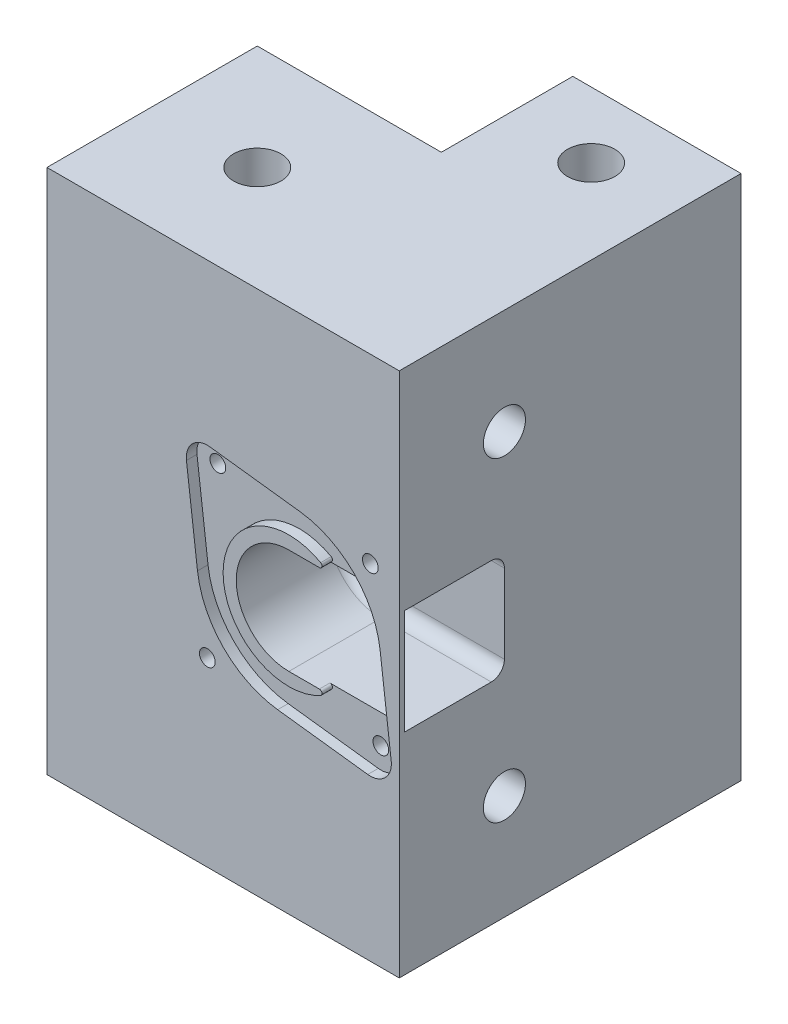
SolidWorks part; units mm, degrees
ref_plane "Front Plane" through (0, 0, 0) normal (0, 0, 1) x (1, 0, 0)
ref_plane "Top Plane" through (0, 0, 0) normal (0, 1, 0) x (1, 0, 0)
ref_plane "Right Plane" through (0, 0, 0) normal (1, 0, 0) x (0, 0, -1)
sketch "Sketch1" plane through (0, 0, 0) normal (0, 1, 0) x (1, 0, 0)
  line L19 (0, -40) -> (0, 0) construction
  line L24 (-25, 0) -> (-5, -40) construction
  line L25 (0, 25) -> (-25, 25) construction
  line L26 (-25, 25) -> (-25, 0) construction
  line L27 (0, 25) -> (32, 0) construction
  line L28 (32, 0) -> (0, 0) construction
  line L29 (-35, 0) -> (0, 0)
  line L30 (-35, -40) -> (-35, 0)
  line L31 (32, -40) -> (-35, -40)
  line L32 (32, 25) -> (32, -40)
  line L33 (0, 25) -> (32, 25)
  line L34 (0, 0) -> (0, 25)
  line L35 (-5, 5) -> (-5, -40) construction
  line L36 (-25, 25) -> (-5, 25) construction
  line L37 (-25, 25) -> (-25, 5) construction
  line L38 (-25, 5) -> (-5, 5) construction
  line L39 (-5, 25) -> (-5, 5) construction
  line L40 (16, 12.5) -> (-5, 22.5) construction
  line L41 (-25, 2.5) -> (-5, 2.5) construction
  line L42 (-25, 2.5) -> (-25, 22.5) construction
  line L43 (-25, 22.5) -> (-5, 22.5) construction
  line L44 (-5, 2.5) -> (-5, 22.5) construction
  line L45 (-25, 2.5) -> (-5, 22.5) construction
  line L46 (-25, 22.5) -> (-5, 2.5) construction
  line L47 (16, 12.5) -> (-5, 2.5) construction
  circle A10 centre (-15, -20) radius 16 construction
  circle A11 centre (-15, -20) radius 6.75 construction
  circle A12 centre (16, 12.5) radius 6 construction
  circle A13 centre (16, 12.5) radius 11 construction
  circle A14 centre (-15, -20) radius 4.5
  circle A15 centre (16, 12.5) radius 4.5
  point P1 (-15, 12.5)
  dimension "D4" = 40
  dimension "D6" = 9
  dimension "D3" = 32
  dimension "D5" = 20
  dimension "D7" = 13.5
  dimension "D8" = 32
  dimension "D9" = 9
  dimension "D10" = 12
  dimension "D11" = 22
  dimension "D1" = 25
  dimension "D2" = 25
  dimension "D12" = 20
extrude "Boss-Extrude1" add sketch "Sketch1" along normal blind 100
sketch "Sketch4" plane through (0, 0, 0) normal (0, -1, 0) x (-1, 0, 0)
  point P0 (15, -20)
hole_wizard "CBORE for M5 Hex Head Bolt2" positions "Sketch4" profile "Sketch5" counterbore size "M5" standard "ANSI Metric"
sketch "Sketch5" plane through (-15, 0, 20) normal (1, 0, 0) x (0, 0, -1)
  line L0 (0, 0) -> (0, 23.85)
  line L1 (0, 23.85) -> (6.75, 23.85)
  line L2 (6.75, 23.85) -> (6.75, 5)
  line L3 (6.75, 5) -> (16, 5)
  line L4 (16, 5) -> (16, 0)
  line L5 (16, 0) -> (0, 0)
  line L10 (0, 23.85) -> (-6.75, 23.85) construction
  line L11 (0, -6.35) -> (0, 107.95) construction
  dimension "Hole Dia." = 13.5
  dimension "Hole Depth" = 23.85
  dimension "C'Bore Dia." = 32
  dimension "C'Bore Depth" = 5
  dimension "Drill Angle" = 180
sketch "Sketch6" plane through (0, 0, 0) normal (0, -1, 0) x (-1, 0, 0)
  point P0 (-16, 12.5)
hole_wizard "CBORE for M5 Hex Head Bolt3" positions "Sketch6" profile "Sketch7" counterbore size "M5" standard "ANSI Metric"
sketch "Sketch7" plane through (16, 0, -12.5) normal (1, 0, 0) x (0, 0, -1)
  line L0 (0, 0) -> (0, 13.5)
  line L1 (0, 13.5) -> (5.1, 13.5)
  line L2 (5.1, 13.5) -> (5.1, 3.5)
  line L3 (5.1, 3.5) -> (11, 3.5)
  line L4 (11, 3.5) -> (11, 0)
  line L5 (11, 0) -> (0, 0)
  line L10 (0, 13.5) -> (-5.1, 13.5) construction
  line L11 (0, -6.35) -> (0, 107.95) construction
  dimension "Hole Dia." = 10.2
  dimension "Hole Depth" = 13.5
  dimension "C'Bore Dia." = 22
  dimension "C'Bore Depth" = 3.5
  dimension "Drill Angle" = 180
sketch "Sketch8" plane through (32, 0, 0) normal (1, 0, 0) x (0, 0, -1)
  line L0 (0, 100) -> (0, 0) construction
  line L1 (-40, 100) -> (25, 100) construction
  line L2 (0, 100) -> (-40, 0) construction
  line L3 (-40, 100) -> (-40, 0) construction
  line L4 (-40, 0) -> (25, 0) construction
  line L5 (-20, 100) -> (-20, 0) construction
  circle A0 centre (-20, 80) radius 4
  circle A1 centre (-20, 20) radius 4
  point P12 (-20, 50)
  dimension "D1" = 8
  dimension "D2" = 60
  dimension "D3" = 30
extrude "Cut-Extrude1" cut sketch "Sketch8" against normal blind 27
sketch "Sketch9" plane through (0, 0, 40) normal (0, 0, 1) x (1, 0, 0)
  line L0 (-10, 100) -> (-10, 0) construction
  line L2 (-35, 100) -> (32, 100) construction
  line L3 (-35, 0) -> (32, 0) construction
  line L4 (-4.5, 34.5) -> (26.5, 34.5) construction
  line L5 (32, 100) -> (32, 0) construction
  line L6 (32, 100) -> (-10, 0) construction
  line L7 (-4.5, 34.5) -> (-4.5, 65.5) construction
  line L8 (-4.5, 65.5) -> (26.5, 65.5) construction
  line L9 (26.5, 34.5) -> (26.5, 65.5) construction
  line L10 (-4.5, 34.5) -> (26.5, 65.5) construction
  line L11 (-4.5, 65.5) -> (26.5, 34.5) construction
  circle A0 centre (-4.5, 65.5) radius 1.5
  circle A1 centre (26.5, 65.5) radius 1.5
  circle A2 centre (26.5, 34.5) radius 1.5
  circle A3 centre (-4.5, 34.5) radius 1.5
  point P4 (11, 50)
  dimension "D3" = 3
  dimension "D1" = 42
  dimension "D2" = 31
  dimension "D4" = 2
  dimension "D5" = 2
extrude "Cut-Extrude2" cut sketch "Sketch9" against normal blind 119
sketch "Sketch10" plane through (0, 0, 40) normal (0, 0, 1) x (1, 0, 0)
  line L0 (-4.5, 65.5) -> (26.5, 65.5) construction
  line L1 (26.5, 65.5) -> (26.5, 34.5) construction
  line L2 (26.5, 34.5) -> (-4.5, 34.5) construction
  line L3 (-4.5, 34.5) -> (-4.5, 65.5) construction
  line L4 (-4.5, 65.5) -> (26.5, 34.5) construction
  line L5 (26.5, 65.5) -> (-4.5, 34.5) construction
  circle A0 centre (11, 50) radius 10
  dimension "D1" = 20
sketch "Sketch11" plane through (32, 0, 0) normal (1, 0, 0) x (0, 0, -1)
  line L0 (-20, 80) -> (-20, 20) construction
  line L1 (-20, 50) -> (-40, 50) construction
  line L2 (-39, 40) -> (-20, 40)
  line L3 (-39, 40) -> (-39, 60)
  line L4 (-39, 60) -> (-20, 60)
  line L5 (-20, 40) -> (-20, 60)
  line L6 (-39, 40) -> (-20, 60) construction
  line L7 (-39, 60) -> (-20, 40) construction
  line L9 (-40, 60) -> (-40, 40) construction
  line L10 (-40, 65.5) -> (-40, 34.5) construction
  point P4 (-20, 50)
  point P13 (-29.5, 50)
  dimension "D1" = 20
  dimension "D2" = 20
  dimension "D3" = 1
extrude "Cut-Extrude3" cut sketch "Sketch10" against normal blind 20 contours A0
extrude "Cut-Extrude4" cut sketch "Sketch11" against normal blind 21
fillet "Fillet2" radius 2.5 3 edges at (21.5, 40, 20) (1, 50, 20) (21.5, 60, 20)
sketch "Sketch13" plane through (0, 0, 40) normal (0, 0, 1) x (1, 0, 0)
  circle A0 centre (-4.5, 65.5) radius 3
  circle A1 centre (26.5, 65.5) radius 3
  circle A2 centre (26.5, 34.5) radius 3
  circle A3 centre (-4.5, 34.5) radius 3
  dimension "D1" = 6
extrude "Cut-Extrude8" cut sketch "Sketch13" against normal up to next from offset 5 offset against normal yes
sketch "Sketch15" plane through (0, 0, 40) normal (0, 0, 1) x (1, 0, 0)
  line L0 (30.4703, 34.9864) -> (28.3701, 52.1282)
  line L1 (26.0136, 30.5297) -> (8.8718, 32.6299)
  line L2 (-4.0138, 69.4706) -> (13.1284, 67.3701)
  line L3 (-8.4706, 65.0138) -> (-6.3701, 47.8718)
  line L4 (-4.5003, 65.5003) -> (26.5, 34.5) construction
  line L5 (-1.5, 50) -> (23.5, 50) construction
  line L6 (11, 60) -> (16.8095, 60)
  line L8 (11, 40) -> (16.8095, 40)
  arc A0 (17.0515, 60.9375) -> (17.0515, 39.0625) centre (11, 50) ccw
  arc A1 (-6.3701, 47.8718) -> (8.8718, 32.6299) centre (11, 50) ccw
  arc A2 (-4.0138, 69.4706) -> (-8.4706, 65.0138) centre (-4.5003, 65.5003) ccw
  arc A3 (26.0136, 30.5297) -> (30.4703, 34.9864) centre (26.5, 34.5) ccw
  arc A4 (28.3701, 52.1282) -> (13.1284, 67.3701) centre (11, 50) ccw
  arc A6 (11, 40) -> (11, 60) centre (11, 50) ccw
  circle A7 centre (11, 50) radius 12.5 construction
  arc A8 (16.8095, 40) -> (17.0515, 39.0625) centre (16.8095, 39.5) cw
  arc A9 (16.8095, 60) -> (17.0515, 60.9375) centre (16.8095, 60.5) ccw
  point P5 (11, 50)
  dimension "D1" = 25
  dimension "D2" = 17.5
  dimension "D3" = 8
  dimension "D4" = 8
  dimension "D10" = 20
  dimension "D11" = 0.5
  dimension "D5" = 43.841
  dimension "D6" = 45
  dimension "D7" = 17.1417
  dimension "D8" = 17.1417
  dimension "D9" = 17.142
extrude "Cut-Extrude9" cut sketch "Sketch15" against normal blind 2
